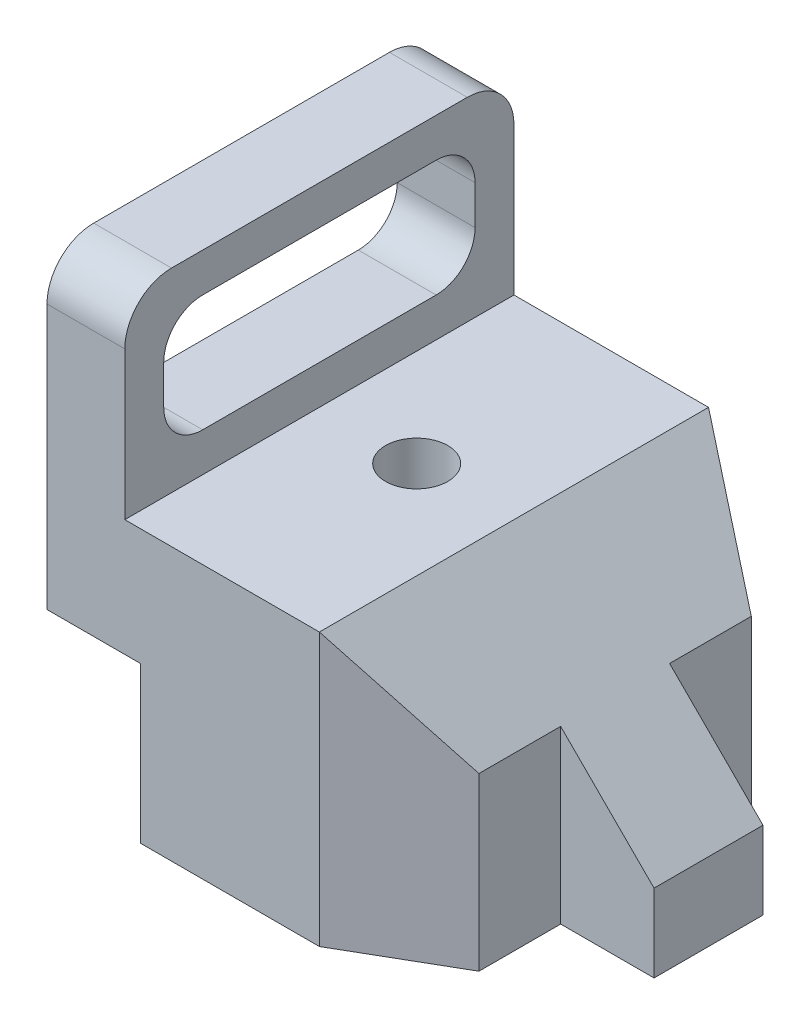
SolidWorks part; units mm, degrees
material "Cast Alloy Steel"
ref_plane "Front Plane" through (0, 0, 0) normal (0, 0, 1) x (1, 0, 0)
ref_plane "Top Plane" through (0, 0, 0) normal (0, 1, 0) x (1, 0, 0)
ref_plane "Right Plane" through (0, 0, 0) normal (1, 0, 0) x (0, 0, -1)
sketch "Sketch2" plane through (0, 0, 0) normal (0, 0, 1) x (1, 0, 0)
  line L0 (-25, 35) -> (0, 10)
  line L1 (-25, 35) -> (0, 35)
  line L2 (-25, 35) -> (-25, 0)
  line L3 (-25, 0) -> (0, 0)
  line L4 (0, 35) -> (0, 0)
  line L5 (-48, 20) -> (-60, 20)
  line L6 (-25, 35) -> (-48, 35)
  line L7 (-25, 35) -> (-25, 0)
  line L8 (-25, 0) -> (-48, 0)
  line L9 (-48, 35) -> (-48, 0)
  line L10 (-48, 35) -> (-60, 35)
  line L11 (-48, 35) -> (-48, 0)
  line L12 (-48, 0) -> (-60, 0)
  line L13 (-60, 35) -> (-60, 0)
  line L15 (-60, 35) -> (-50, 35)
  line L16 (-60, 35) -> (-60, 60)
  line L17 (-60, 60) -> (-50, 60)
  line L18 (-50, 35) -> (-50, 60)
  dimension "D1" = 25
  dimension "D2" = 35
  dimension "D3" = 45
  dimension "D4" = 23
  dimension "D5" = 60
  dimension "D6" = 20
  dimension "D7" = 10
  dimension "D8" = 25
extrude "Boss-Extrude1" add sketch "Sketch2" along normal mid plane 50 contours L10 L18 L17 L16 | L10 L13 L5 L9 | L6 L9 L8 L2 | L4 L0 L2 L3 region at (-14.8148, 12.4074, 0) region at (-36.5, 17.5, 0) region at (-54, 27.5, 0) region at (-55, 47.5, 0)
sketch "Sketch3" plane through (0, 0, 0) normal (0, 1, 0) x (1, 0, 0)
  line L0 (-50, 25) -> (-60, 25) construction
  line L1 (-60, 25) -> (-60, -25) construction
  line L2 (-60, -25) -> (-50, -25) construction
  line L3 (-50, -25) -> (-50, 25) construction
  line L4 (0, 25) -> (-25, 25) construction
  line L5 (-25, -25) -> (0, -25) construction
  line L6 (0, -25) -> (0, 25) construction
  line L7 (-25, 25) -> (-50, 25) construction
  line L8 (-50, 25) -> (-50, -25) construction
  line L9 (-50, -25) -> (-25, -25) construction
  line L10 (-50, 25) -> (-60, 25)
  line L11 (-60, 25) -> (-60, -25)
  line L12 (-60, -25) -> (-50, -25)
  line L13 (-50, -25) -> (-50, 25)
  line L14 (0, 25) -> (-25, 25)
  line L15 (-25, -25) -> (0, -25)
  line L16 (0, -25) -> (0, 25)
  line L17 (-25, 25) -> (-50, 25)
  line L18 (-50, 25) -> (-50, -25)
  line L19 (-50, -25) -> (-25, -25)
  line L20 (-37.5, 25) -> (-37.5, -25) construction
  line L21 (-50, 0) -> (-25, 0) construction
  line L22 (-25, -25) -> (-25, 25) construction
  line L23 (-25, 25) -> (0, 10.5662)
  line L24 (-12.5, 25) -> (-12.5, -25) construction
  line L25 (-25, 0) -> (0, 0) construction
  line L26 (-25, -25) -> (0, -10.5662)
  line L27 (-12, -7) -> (-12, -17.4944)
  line L28 (0, 7) -> (-12, 7)
  line L29 (0, 7) -> (0, -7)
  line L30 (0, -7) -> (-12, -7)
  line L31 (-12, 7) -> (-12, -7)
  line L32 (-12, 7) -> (-12, 17.4944)
  circle A0 centre (-37.5, 0) radius 4
  point P28 (-12, 0)
  dimension "D1" = 8
  dimension "D2" = 30
  dimension "D3" = 14
  dimension "D4" = 12
extrude "Cut-Extrude2" cut sketch "Sketch3" along normal through all contours A0 region at (-37.5, 0, 0)
extrude "Cut-Extrude3" cut sketch "Sketch3<5>" along normal through all contours L14 L23 L16 | L26 L15 L16 region at (-8.3333, 0, -20.1887) region at (-8.3333, 0, 20.1887)
sketch "Sketch3<5>" plane through (0, 0, 0) normal (0, 1, 0) x (1, 0, 0) same geometry as "Sketch3"
extrude "Cut-Extrude4" cut sketch "Sketch3<6>" along normal through all contours L32 L28 L16 L23 | L16 L30 L27 L26 region at (-6.9855, 0, -10.7997) region at (-6.9855, 0, 10.7997)
sketch "Sketch3<6>" plane through (0, 0, 0) normal (0, 1, 0) x (1, 0, 0) same geometry as "Sketch3"
ref_plane "Plane1" through (-50, 0, 0) normal (1, 0, 0) x (0, 0, -1)
sketch "Sketch6" plane through (-50, 0, 0) normal (1, 0, 0) x (0, 0, -1)
  line L0 (0, 60) -> (0, 35) construction
  line L1 (-25, 47.5) -> (25, 47.5) construction
  line L3 (-15, 55) -> (15, 55)
  line L4 (25, 35) -> (25, 60)
  line L5 (25, 60) -> (-25, 60)
  line L6 (-25, 60) -> (-25, 35)
  line L7 (-25, 35) -> (25, 35)
  line L8 (25, 35) -> (25, 60)
  line L9 (25, 60) -> (-25, 60)
  line L10 (-25, 60) -> (-25, 35)
  line L11 (-25, 35) -> (25, 35)
  line L12 (-20, 50) -> (-20, 45)
  line L13 (-15, 40) -> (15, 40)
  line L14 (20, 50) -> (20, 45)
  line L15 (-20, 55) -> (20, 40) construction
  line L16 (-20, 40) -> (20, 55) construction
  arc A0 (20, 50) -> (15, 55) centre (15, 50) ccw
  arc A1 (15, 40) -> (20, 45) centre (15, 45) ccw
  arc A2 (-20, 45) -> (-15, 40) centre (-15, 45) ccw
  arc A3 (-15, 55) -> (-20, 50) centre (-15, 50) ccw
  point P8 (0, 47.5)
  dimension "D4" = 5
  dimension "D2" = 15
  dimension "D3" = 40
  dimension "D1" = 0
extrude "Cut-Extrude5" cut sketch "Sketch6" against normal through all contours L12 A2 L13 A1 L14 A0 L3 A3
fillet "Fillet1" radius 6 2 edges at (-55, 60, -25) (-55, 60, 25)
